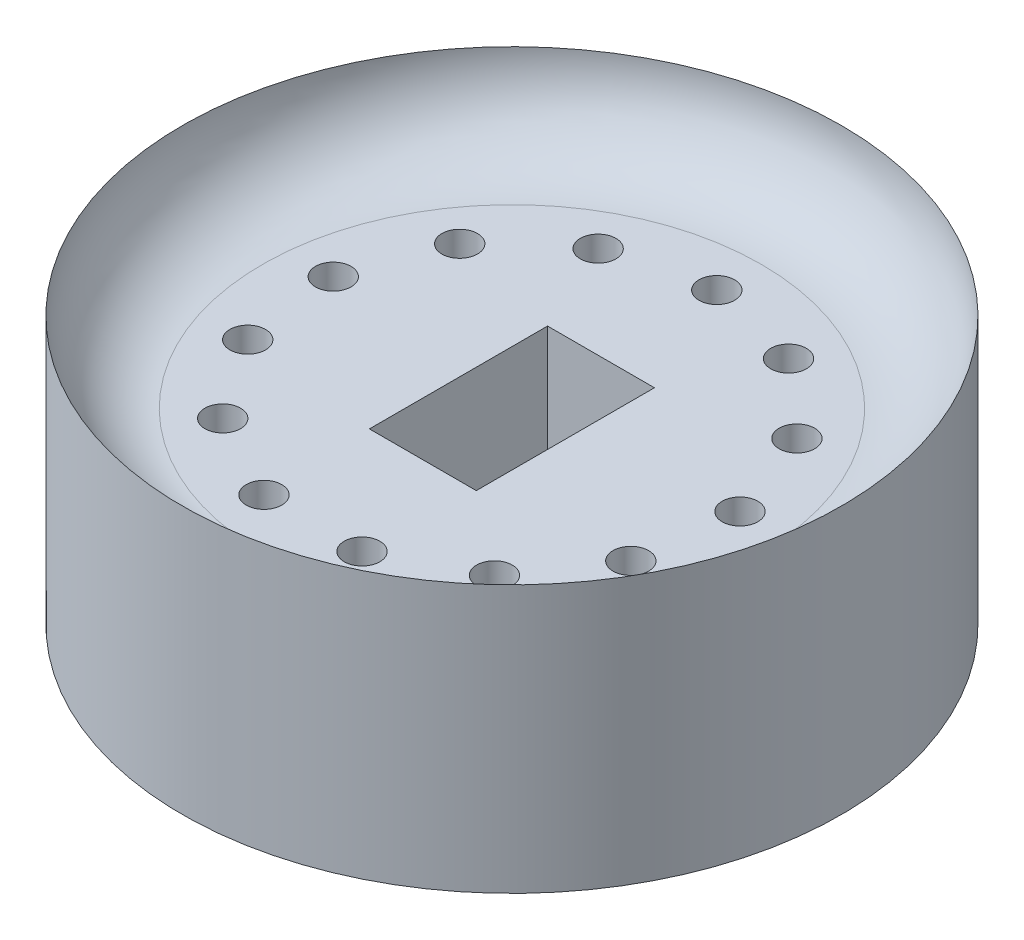
SolidWorks part; units mm, degrees
ref_plane "Alzado" through (0, 0, 0) normal (0, 0, 1) x (1, 0, 0)
ref_plane "Planta" through (0, 0, 0) normal (0, 1, 0) x (1, 0, 0)
ref_plane "Vista lateral" through (0, 0, 0) normal (1, 0, 0) x (0, 0, -1)
sketch "Croquis1" plane through (0, 0, 0) normal (0, 0, 1) x (1, 0, 0)
  line L0 (7, 5.25) -> (0, 5.25)
  line L1 (0, 0) -> (9.25, 0)
  line L2 (0, 0) -> (0, 7.5)
  line L3 (0, 7.5) -> (9.25, 7.5)
  line L4 (9.25, 0) -> (9.25, 7.5)
  circle A0 centre (7, 7.5) radius 2.25
  dimension "D1" = 9.25
  dimension "D2" = 7.5
  dimension "D3" = 7
revolve "Revolución3" add sketch "Croquis1" angle 360 about L2 region at (4.7152, 2.6934, 0)
sketch "Croquis2" plane through (0, 5.25, 0) normal (0, 1, 0) x (1, 0, 0)
  line L1 (-1.5, -2.5) -> (1.5, -2.5)
  line L2 (-1.5, -2.5) -> (-1.5, 2.5)
  line L3 (-1.5, 2.5) -> (1.5, 2.5)
  line L4 (1.5, -2.5) -> (1.5, 2.5)
  line L5 (-1.5, -2.5) -> (1.5, 2.5) construction
  line L6 (-1.5, 2.5) -> (1.5, -2.5) construction
  circle A0 centre (0, 0) radius 5.75
  circle A1 centre (0, 5.75) radius 0.5
  circle A2 centre (2.6722, 5.0914) radius 0.5
  circle A3 centre (4.7322, 3.2664) radius 0.5
  circle A4 centre (5.7081, 0.6931) radius 0.5
  circle A5 centre (5.3763, -2.039) radius 0.5
  circle A6 centre (3.813, -4.3039) radius 0.5
  circle A7 centre (1.3761, -5.5829) radius 0.5
  circle A8 centre (-1.3761, -5.5829) radius 0.5
  circle A9 centre (-3.813, -4.3039) radius 0.5
  circle A10 centre (-5.3763, -2.039) radius 0.5
  circle A11 centre (-5.7081, 0.6931) radius 0.5
  circle A12 centre (-4.7322, 3.2664) radius 0.5
  circle A13 centre (-2.6722, 5.0914) radius 0.5
  dimension "D1" = 11.5
  dimension "D2" = 1
  dimension "D4" = 3
  dimension "D5" = 5
  dimension "D3" = 13
extrude "Cortar-Extruir1" cut sketch "Croquis2" against normal through all contours A1 | A2 | A3 | A4 | A5 | A6 | A7 | A8 | A9 | A10 | A11 | A12 | A13 | L4 L3 L2 L1
